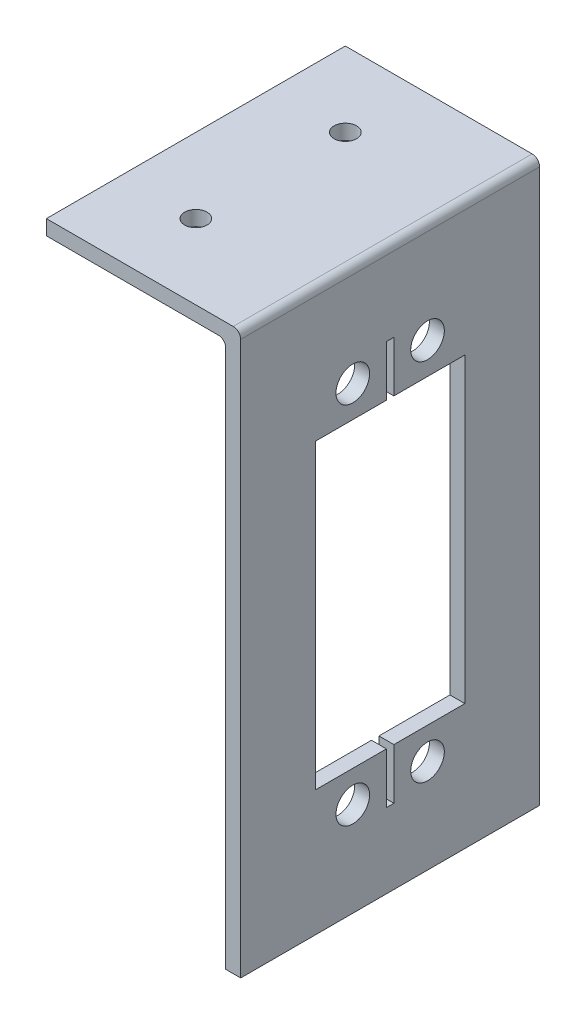
SolidWorks part; units mm, degrees
ref_plane "Front Plane" through (0, 0, 0) normal (0, 0, 1) x (1, 0, 0)
ref_plane "Top Plane" through (0, 0, 0) normal (0, 1, 0) x (1, 0, 0)
ref_plane "Right Plane" through (0, 0, 0) normal (1, 0, 0) x (0, 0, -1)
sketch "Sketch1" plane through (0, 0, 0) normal (0, 1, 0) x (1, 0, 0)
  line L1 (0, 0) -> (25, 0)
  line L2 (0, 0) -> (0, 40)
  line L3 (0, 40) -> (25, 40)
  line L4 (25, 0) -> (25, 40)
  circle A1 centre (10, 30) radius 1.5
  circle A2 centre (10, 10) radius 1.5
  dimension "D3" = 3
  dimension "D4" = 10
  dimension "D5" = 15
  dimension "D6" = 10
  dimension "D7" = 15
  dimension "D1" = 40
  dimension "D2" = 25
extrude "Boss-Extrude1" add sketch "Sketch1" along normal blind 2
sketch "Sketch2" plane through (0, 2, 0) normal (0, 1, 0) x (1, 0, 0)
  line L0 (0, 0) -> (25, 0) construction
  line L1 (25, 40) -> (24, 40)
  line L3 (25, 0) -> (24, 0)
  line L4 (24, 40) -> (24, 0)
  line L6 (25, 40) -> (26, 40)
  line L8 (25, 0) -> (26, 0)
  line L9 (26, 40) -> (26, 0)
  dimension "D1" = 1
  dimension "D2" = 1
extrude "Boss-Extrude2" add sketch "Sketch2" against normal blind 75
fillet "Fillet1" radius 1 2 edges at (24, 0, -20) (26, 2, -20)
sketch "Sketch3" plane through (24, 0, 0) normal (-1, 0, 0) x (0, 0, 1)
  line L0 (-20, -9) -> (-19.5, -9)
  line L1 (-20, -9) -> (-20, -15.8)
  line L2 (-20, -15.8) -> (-19.5, -15.8)
  line L3 (-19.5, -9) -> (-19.5, -15.8)
  line L4 (-20, -9) -> (-20.5, -9)
  line L5 (-20, -9) -> (-20, -15.8)
  line L6 (-20, -15.8) -> (-20.5, -15.8)
  line L7 (-20.5, -9) -> (-20.5, -15.8)
  line L8 (-20, -15.8) -> (-10, -15.8)
  line L9 (-20, -15.8) -> (-20, -56.2)
  line L10 (-20, -56.2) -> (-10, -56.2)
  line L11 (-10, -15.8) -> (-10, -56.2)
  line L12 (-20, -15.8) -> (-30, -15.8)
  line L13 (-20, -15.8) -> (-20, -56.2)
  line L14 (-20, -56.2) -> (-30, -56.2)
  line L15 (-30, -15.8) -> (-30, -56.2)
  line L16 (-20, -56.2) -> (-19.5, -56.2)
  line L17 (-20, -56.2) -> (-20, -63)
  line L18 (-20, -63) -> (-19.5, -63)
  line L19 (-19.5, -56.2) -> (-19.5, -63)
  line L20 (-20, -56.2) -> (-20.5, -56.2)
  line L21 (-20, -56.2) -> (-20, -63)
  line L22 (-20, -63) -> (-20.5, -63)
  line L23 (-20.5, -56.2) -> (-20.5, -63)
  line L24 (-40, -73) -> (0, -73) construction
  line L25 (-40, -73) -> (-40, -1) construction
  line L26 (0, -73) -> (0, -1) construction
  circle A0 centre (-25, -11.6) radius 2.25
  circle A1 centre (-15, -11.6) radius 2.25
  circle A2 centre (-15, -60.4) radius 2.25
  circle A3 centre (-25, -60.4) radius 2.25
  dimension "D1" = 0.5
  dimension "D2" = 0.5
  dimension "D3" = 6.8
  dimension "D4" = 40.4
  dimension "D5" = 10
  dimension "D6" = 10
  dimension "D7" = 4.5
  dimension "D8" = 4.2
  dimension "D9" = 4.5
  dimension "D10" = 4.2
  dimension "D11" = 0.5
  dimension "D12" = 0.5
  dimension "D13" = 6.8
  dimension "D14" = 4.2
  dimension "D15" = 4.5
  dimension "D16" = 4.5
  dimension "D17" = 4.2
  dimension "D18" = 10
  dimension "D19" = 10
  dimension "D20" = 10
extrude "Cut-Extrude1" cut sketch "Sketch3" against normal blind 75 contours A3 | L12 L15 L14 L9 L6 | A2 | L14 L23 L22 L17 | L19 L10 L17 L18 | L11 L8 L2 L9 L10 | A1 | A0 | L4 L7 L6 L1 | L3 L0 L1 L2 region at (24, -12.4, -19.75) region at (24, -12.4, -20.25) region at (24, -36, -25) region at (24, -36, -15) region at (24, -59.6, -20.25) region at (24, -59.6, -19.75) region at (24, -11.6, -25) region at (24, -11.6, -15) region at (24, -60.4, -15) region at (24, -60.4, -25)
